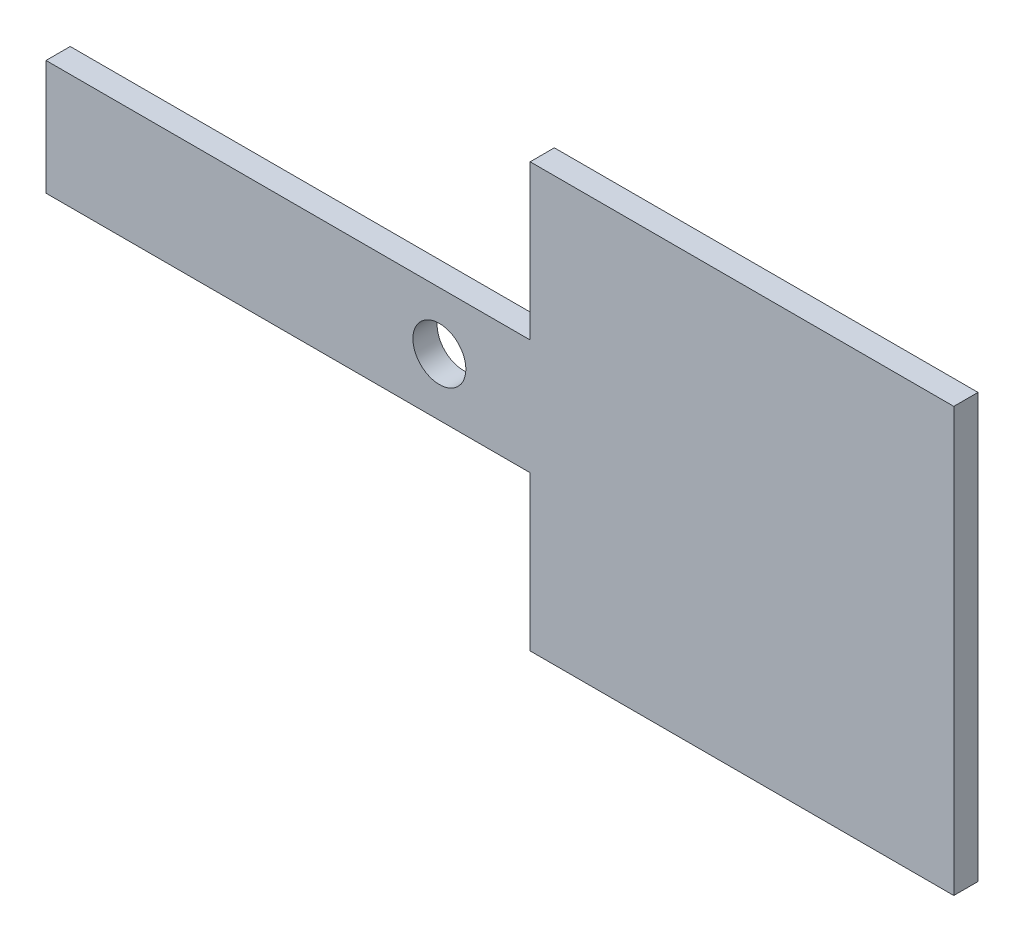
SolidWorks part; units mm, degrees
ref_plane "Front Plane" through (0, 0, 0) normal (0, 0, 1) x (1, 0, 0)
ref_plane "Top Plane" through (0, 0, 0) normal (0, 1, 0) x (1, 0, 0)
ref_plane "Right Plane" through (0, 0, 0) normal (1, 0, 0) x (0, 0, -1)
sketch "Sketch1" plane through (0, 0, 0) normal (0, 0, 1) x (1, 0, 0)
  line L0 (0, 0) -> (-6, 0) construction
  line L1 (0, 14) -> (28, 14)
  line L2 (0, 14) -> (0, -14)
  line L3 (0, -14) -> (28, -14)
  line L4 (28, 14) -> (28, -14)
  line L5 (-32, 3.8) -> (0, 3.8)
  line L6 (-32, 3.8) -> (-32, -3.8)
  line L7 (-32, -3.8) -> (0, -3.8)
  line L8 (0, 3.8) -> (0, -3.8)
  circle A0 centre (-6, 0) radius 1.75
  point P4 (0, 0)
  point P10 (0, 0)
  dimension "D5" = 3.5
  dimension "D1" = 28
  dimension "D2" = 28
  dimension "D3" = 7.6
  dimension "D4" = 60
  dimension "D6" = 26
  dimension "D7" = 34
extrude "Boss-Extrude1" add sketch "Sketch1" along normal blind 1.6 contours L6 L7 L8 A0 L2 L5 | L4 L1 L2 L8 L3 region at (14, 0, 0) region at (-16.4119, 0, 0)
